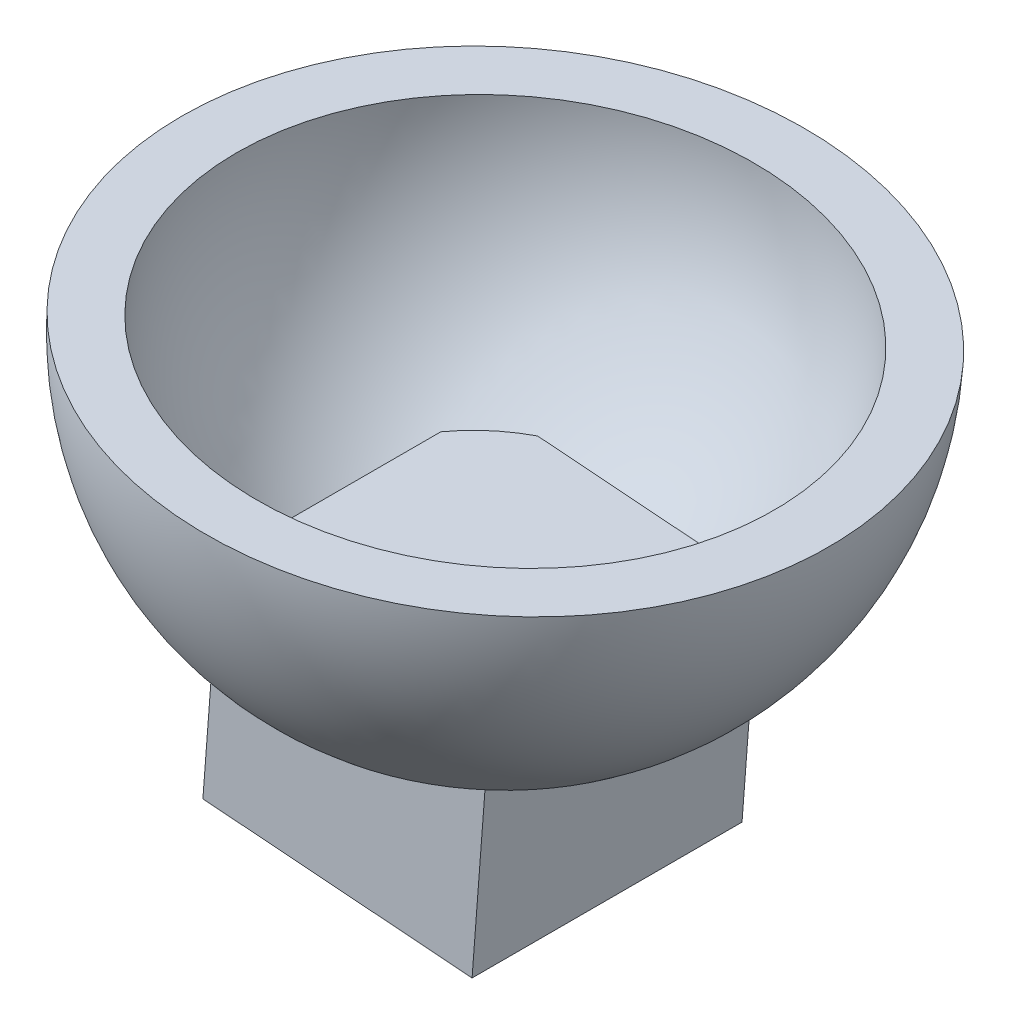
SolidWorks part; units mm, degrees
ref_plane "Front Plane" through (0, 0, 0) normal (0, 0, 1) x (1, 0, 0)
ref_plane "Top Plane" through (0, 0, 0) normal (0, 1, 0) x (1, 0, 0)
ref_plane "Right Plane" through (0, 0, 0) normal (1, 0, 0) x (0, 0, -1)
sketch "Sketch1" plane through (0, 0, 0) normal (0, 0, 1) x (1, 0, 0)
  line L0 (-63.202, 4.8194) -> (0, 0) construction
  line L1 (0, 0) -> (-4.8194, -63.202) construction
  line L2 (-76.1237, 5.8048) -> (-63.202, 4.8194)
  line L3 (-5.8048, -76.1237) -> (-4.8194, -63.202)
  arc A0 (-63.202, 4.8194) -> (-4.8194, -63.202) centre (0, 0) ccw
  arc A1 (-76.1237, 5.8048) -> (-5.8048, -76.1237) centre (0, 0) ccw
revolve "Revolve1" add sketch "Sketch1" angle 360 about L1
sketch "Sketch2" plane through (0, 0, 0) normal (0.076, 0.9971, 0) x (0.9971, -0.076, 0)
  line L1 (-19.7422, -26.506) -> (19.7422, -26.506)
  line L2 (-19.7422, -26.506) -> (-19.7422, 26.506)
  line L3 (-19.7422, 26.506) -> (19.7422, 26.506)
  line L4 (19.7422, -26.506) -> (19.7422, 26.506)
  line L5 (-19.7422, -26.506) -> (19.7422, 26.506) construction
  line L6 (-19.7422, 26.506) -> (19.7422, -26.506) construction
  point P0 (0, 0)
ref_plane "Plane2" through (0, 0, 0) normal (0.076, 0.9971, 0) x (0.9971, -0.076, 0)
ref_axis "Axis1" through (0, 0, 0) along (0.076, 0.9971, 0)
ref_plane "Plane3" through (-5.8048, -76.1237, 0) normal (-0.076, -0.9971, 0) x (-0.9971, 0.076, 0)
sketch "Sketch3" plane through (-5.8048, -76.1237, 0) normal (-0.076, -0.9971, 0) x (-0.9971, 0.076, 0)
  line L1 (31.75, -31.75) -> (-31.75, -31.75)
  line L2 (31.75, -31.75) -> (31.75, 31.75)
  line L3 (31.75, 31.75) -> (-31.75, 31.75)
  line L4 (-31.75, -31.75) -> (-31.75, 31.75)
  line L5 (31.75, -31.75) -> (-31.75, 31.75) construction
  line L6 (31.75, 31.75) -> (-31.75, -31.75) construction
  point P0 (0, 0)
  dimension "D1" = 63.5
  dimension "D2" = 63.5
extrude "Boss-Extrude2" add sketch "Sketch3" along normal blind 25.4 and the other way blind 25.4
